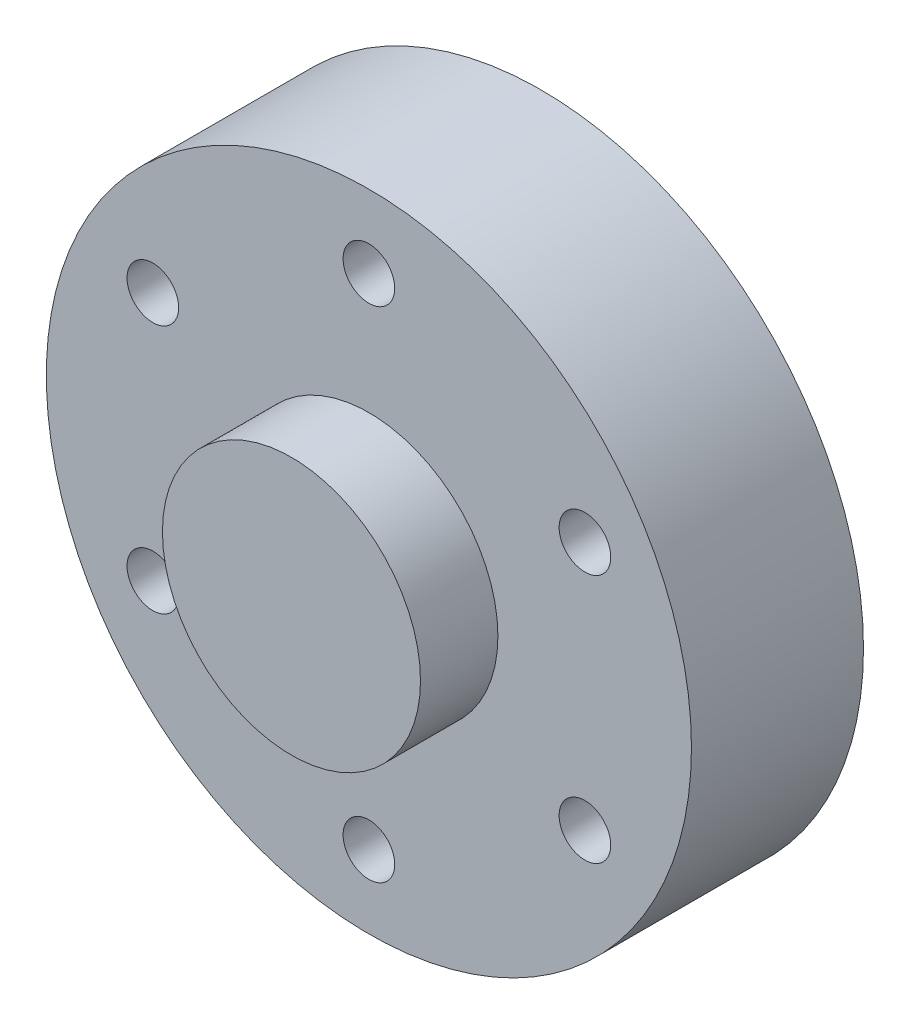
SolidWorks part; units mm, degrees
ref_plane "Front Plane" through (0, 0, 0) normal (0, 0, 1) x (1, 0, 0)
ref_plane "Top Plane" through (0, 0, 0) normal (0, 1, 0) x (1, 0, 0)
ref_plane "Right Plane" through (0, 0, 0) normal (1, 0, 0) x (0, 0, -1)
sketch "Sketch2" plane through (0, 0, 0) normal (0, 0, 1) x (1, 0, 0)
  circle A0 centre (0, 0) radius 9.5
  circle A1 centre (0, 0) radius 14.5 construction
  circle A3 centre (0, 0) radius 18.75
  circle A4 centre (0, 14.5) radius 1.5
  circle A5 centre (12.5574, 7.25) radius 1.5
  circle A6 centre (12.5574, -7.25) radius 1.5
  circle A7 centre (0, -14.5) radius 1.5
  circle A8 centre (-12.5574, -7.25) radius 1.5
  circle A9 centre (-12.5574, 7.25) radius 1.5
  point P21 (0, 0)
  dimension "D1" = 19
  dimension "D3" = 29
  dimension "D4" = 37.5
  dimension "D5" = 3
  dimension "D6" = 6
extrude "Boss-Extrude1" add sketch "Sketch2" along normal blind 10 contours A3 A9 A8 A7 A6 A5 A4 A0 | A0 region at (0, 0, 0) region at (-18.2197, 0, 0)
sketch "Sketch3" plane through (0, 0, 10) normal (0, 0, 1) x (1, 0, 0)
  circle A0 centre (0, 0) radius 7.5
  dimension "D1" = 15
extrude "Boss-Extrude2" add sketch "Sketch3" along normal blind 4.5
sketch "Sketch6" plane through (0, 0, 0) normal (0, 0, -1) x (-1, 0, 0)
  circle A0 centre (0, 0) radius 7.5
  dimension "D1" = 15
extrude "Boss-Extrude4" add sketch "Sketch6" along normal blind 4.5 contours A0
sketch "Sketch7" plane through (0, 0, -4.5) normal (0, 0, -1) x (-1, 0, 0)
  circle A0 centre (0, 0) radius 2
  dimension "D1" = 4
extrude "Boss-Extrude5" add sketch "Sketch7" along normal blind 1
fillet "Fillet2" radius 0.05 1 edges at (-2, 0, -5.5)
sketch "Sketch9" plane through (0, 0, -5.5) normal (0, 0, -1) x (-1, 0, 0)
  line L1 (-1.118, 1) -> (1.118, 1)
  arc A0 (-1.118, 1) -> (1.118, 1) centre (0, 0) ccw
  dimension "D1" = 3
extrude "Cut-Extrude1" cut sketch "Sketch9" against normal blind 11
